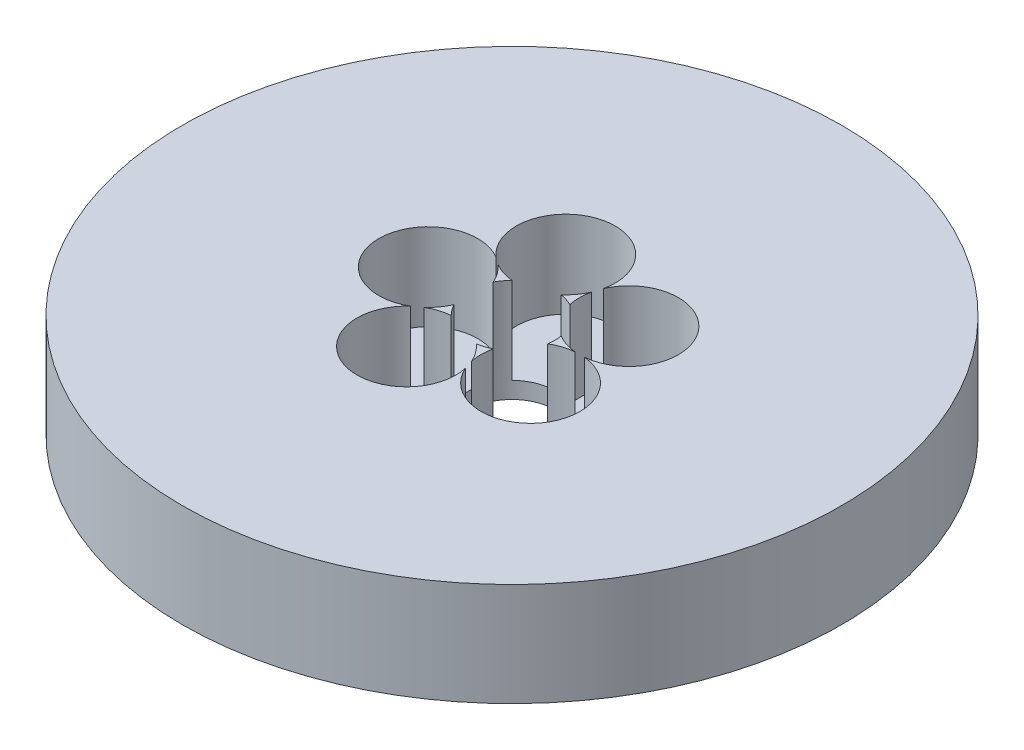
SolidWorks part; units mm, degrees
ref_plane "Front Plane" through (0, 0, 0) normal (0, 0, 1) x (1, 0, 0)
ref_plane "Top Plane" through (0, 0, 0) normal (0, 1, 0) x (1, 0, 0)
ref_plane "Right Plane" through (0, 0, 0) normal (1, 0, 0) x (0, 0, -1)
sketch "Sketch1" plane through (0, 0, 0) normal (0, 1, 0) x (1, 0, 0)
  circle A0 centre (0, 0) radius 57.5
  dimension "FLANGE_OD" = 115
extrude "Boss-Extrude1" add sketch "Sketch1" along normal blind 18
sketch "Sketch2" plane through (0, 0, 0) normal (0, 1, 0) x (1, 0, 0)
  circle A0 centre (0, 0) radius 7.5
  dimension "BORE_D" = 15
extrude "Cut-Extrude1" cut sketch "Sketch2" along normal through all
sketch "Sketch3" plane through (0, 18, 0) normal (0, 1, 0) x (1, 0, 0)
  circle A0 centre (0, 0) radius 14.613 construction
  circle A1 centre (-14.613, 0) radius 8.6294
  dimension "BOLT_D" = 17.2587
  dimension "BOLT_PCD" = 29.226
extrude "Cut-Extrude2" cut sketch "Sketch3" against normal blind 15.116
pattern_circular "CirPattern1" count 5 over 360 about axis through (0, 0, 0) along (0, 1, 0) of "Cut-Extrude2"
